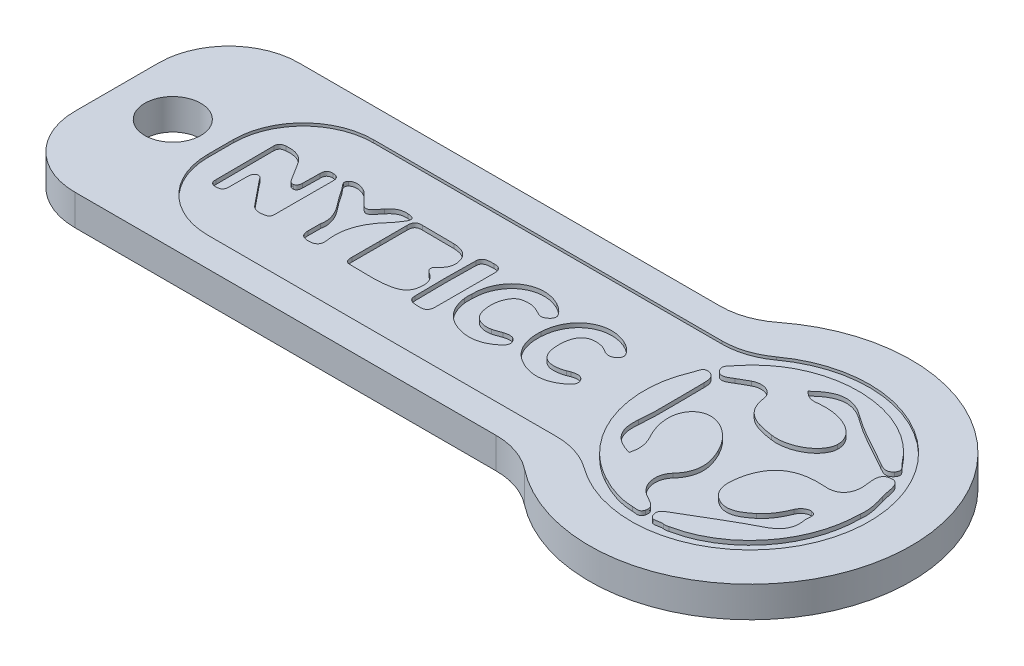
SolidWorks part; units mm, degrees
ref_plane "Plan de face" through (0, 0, 0) normal (0, 0, 1) x (1, 0, 0)
ref_plane "Plan de dessus" through (0, 0, 0) normal (0, 1, 0) x (1, 0, 0)
ref_plane "Plan de droite" through (0, 0, 0) normal (1, 0, 0) x (0, 0, -1)
sketch "Esquisse1" plane through (0, 0, 0) normal (0, 1, 0) x (1, 0, 0)
  line L0 (-14.5, 0) -> (0, 0) construction
  line L1 (-18.5, 8) -> (18.5, 8)
  line L2 (-18.5, 8) -> (-18.5, -8)
  line L3 (-18.5, -8) -> (18.5, -8)
  line L5 (-18.5, 8) -> (18.5, -8) construction
  line L6 (-18.5, -8) -> (18.5, 8) construction
  arc A0 (18.5, -8) -> (18.5, 8) centre (26.7614, 0) ccw
  circle A1 centre (-14.5, 0) radius 2
  point P0 (0, 0)
  dimension "D3" = 23
  dimension "D5" = 4
  dimension "D1" = 37
  dimension "D2" = 16
  dimension "D4" = 4
extrude "Boss.-Extru.1" add sketch "Esquisse1" along normal blind 2
sketch "Esquisse2" plane through (0, 2, 0) normal (0, 1, 0) x (1, 0, 0)
  line L0 (20.6551, -5.913) -> (-11.0872, -5.913)
  line L1 (-11.0872, -5.913) -> (-11.0872, 5.913)
  line L2 (-11.0872, 5.913) -> (20.6551, 5.913)
  line L3 (20.6551, 5.913) -> (20.5787, 5.7726)
  line L7 (18.5, 8) -> (-18.5, 8)
  line L8 (-18.5, 8) -> (-18.5, -8)
  line L9 (-18.5, -8) -> (18.5, -8)
  line L10 (18.5, 8) -> (-18.5, 8)
  line L11 (-18.5, 8) -> (-18.5, -8)
  line L12 (-18.5, -8) -> (18.5, -8)
  arc A2 (20.6551, -5.913) -> (20.6551, 5.913) centre (26.7614, 0) ccw
  arc A3 (20.6551, -5.913) -> (20.6551, 5.913) centre (26.7614, 0) ccw
  arc A4 (18.5, -8) -> (18.5, 8) centre (26.7614, 0) ccw
  arc A5 (18.5, -8) -> (18.5, 8) centre (26.7614, 0) ccw
  spline S0 degree 3 poles (0.225, -1.9246) (0.2286, -1.2609) (0.2275, -0.5975) (0.2283, 0.0661) knots 10 10 10 10 11 11 11 11
  spline S1 degree 3 poles (0.6284, -2.4527) (0.2813, -2.4644) (0.2234, -2.2089) (0.225, -1.9246) knots 9 9 9 9 10 10 10 10
  spline S2 degree 3 poles (3.5067, -2.3468) (2.5542, -2.5708) (1.5879, -2.4206) (0.6284, -2.4527) knots 8 8 8 8 9 9 9 9
  spline S3 degree 3 poles (4.4683, -1.5249) (4.3523, -2.028) (3.9703, -2.238) (3.5067, -2.3468) knots 7 7 7 7 8 8 8 8
  spline S4 degree 3 poles (4.0132, -0.175) (4.5319, -0.4973) (4.5922, -0.9877) (4.4683, -1.5249) knots 6 6 6 6 7 7 7 7
  spline S5 degree 3 poles (3.9341, 0.5259) (3.6149, 0.2483) (3.6818, 0.0309) (4.0132, -0.175) knots 5 5 5 5 6 6 6 6
  spline S6 degree 3 poles (4.2394, 1.8576) (4.4545, 1.3474) (4.3569, 0.8935) (3.9341, 0.5259) knots 4 4 4 4 5 5 5 5
  spline S7 degree 3 poles (3.0323, 2.5476) (3.5345, 2.5261) (4.0161, 2.3873) (4.2394, 1.8576) knots 3 3 3 3 4 4 4 4
  spline S8 degree 3 poles (0.7853, 2.5646) (1.5338, 2.5425) (2.2844, 2.5795) (3.0323, 2.5476) knots 2 2 2 2 3 3 3 3
  spline S9 degree 3 poles (0.2259, 1.9923) (0.215, 2.3984) (0.3606, 2.5772) (0.7853, 2.5646) knots 1 1 1 1 2 2 2 2
  spline S10 degree 3 poles (0.2283, 0.0661) (0.2291, 0.7082) (0.243, 1.3507) (0.2259, 1.9923) knots 0 0 0 0 1 1 1 1
  spline S11 degree 3 poles (-5.1722, 2.1197) (-5.1775, 1.4133) (-5.1754, 0.7068) (-5.176, 0.0003) knots 18 18 18 18 19 19 19 19
  spline S12 degree 3 poles (-5.6399, 2.5867) (-5.3196, 2.5835) (-5.1698, 2.4412) (-5.1722, 2.1197) knots 17 17 17 17 18 18 18 18
  spline S13 degree 3 poles (-6.0939, 2.115) (-6.0989, 2.4345) (-5.9709, 2.5902) (-5.6399, 2.5867) knots 16 16 16 16 17 17 17 17
  spline S14 degree 3 poles (-6.114, 0.896) (-6.0883, 1.3013) (-6.0877, 1.7087) (-6.0939, 2.115) knots 15 15 15 15 16 16 16 16
  spline S15 degree 3 poles (-6.3567, 0.4874) (-6.1454, 0.5282) (-6.1242, 0.7367) (-6.114, 0.896) knots 14 14 14 14 15 15 15 15
  spline S16 degree 3 poles (-6.7563, 0.7516) (-6.663, 0.6061) (-6.5561, 0.4488) (-6.3567, 0.4874) knots 13 13 13 13 14 14 14 14
  spline S17 degree 3 poles (-7.4724, 1.8877) (-7.2442, 1.5028) (-6.998, 1.1285) (-6.7563, 0.7516) knots 12 12 12 12 13 13 13 13
  spline S18 degree 3 poles (-8.9993, 2.5914) (-8.3468, 2.6534) (-7.8223, 2.4779) (-7.4724, 1.8877) knots 11 11 11 11 12 12 12 12
  spline S19 degree 3 poles (-9.4508, 2.1725) (-9.4369, 2.4583) (-9.2899, 2.5782) (-8.9993, 2.5914) knots 10 10 10 10 11 11 11 11
  spline S20 degree 3 poles (-9.4291, -2.0014) (-9.4372, -0.6101) (-9.4441, 0.7812) (-9.4508, 2.1725) knots 9 9 9 9 10 10 10 10
  spline S21 degree 3 poles (-9.0021, -2.437) (-9.2963, -2.4301) (-9.4357, -2.2901) (-9.4291, -2.0014) knots 8 8 8 8 9 9 9 9
  spline S22 degree 3 poles (-8.5069, -2.0014) (-8.512, -2.3343) (-8.6938, -2.4441) (-9.0021, -2.437) knots 7 7 7 7 8 8 8 8
  spline S23 degree 3 poles (-8.5036, -0.717) (-8.5043, -1.1452) (-8.5101, -1.5733) (-8.5069, -2.0014) knots 6 6 6 6 7 7 7 7
  spline S24 degree 3 poles (-8.2858, -0.219) (-8.4821, -0.3042) (-8.5032, -0.5178) (-8.5036, -0.717) knots 5 5 5 5 6 6 6 6
  spline S25 degree 3 poles (-7.8369, -0.4857) (-7.953, -0.3438) (-8.0529, -0.1181) (-8.2858, -0.219) knots 4 4 4 4 5 5 5 5
  spline S26 degree 3 poles (-6.4635, -2.1807) (-6.9172, -1.6123) (-7.376, -1.0481) (-7.8369, -0.4857) knots 3 3 3 3 4 4 4 4
  spline S27 degree 3 poles (-5.4688, -2.4272) (-5.8242, -2.5108) (-6.1923, -2.5206) (-6.4635, -2.1807) knots 2 2 2 2 3 3 3 3
  spline S28 degree 3 poles (-5.1794, -1.7337) (-5.182, -2.003) (-5.1008, -2.3406) (-5.4688, -2.4272) knots 1 1 1 1 2 2 2 2
  spline S29 degree 3 poles (-5.176, 0.0003) (-5.1766, -0.5777) (-5.174, -1.1557) (-5.1794, -1.7337) knots 0 0 0 0 1 1 1 1
  spline S30 degree 3 poles (14.6022, 1.5071) (13.5928, 1.7408) (13.0414, 1.2329) (13.0294, 0.0773) knots 11 11 11 11 12 12 12 12
  spline S31 degree 3 poles (15.1149, 1.2613) (14.9529, 1.3592) (14.7827, 1.4653) (14.6022, 1.5071) knots 10 10 10 10 11 11 11 11
  spline S32 degree 3 poles (15.9779, 1.4079) (15.76, 1.1539) (15.4505, 1.0583) (15.1149, 1.2613) knots 9 9 9 9 10 10 10 10
  spline S33 degree 3 poles (15.7902, 2.127) (15.9828, 1.9215) (16.214, 1.683) (15.9779, 1.4079) knots 8 8 8 8 9 9 9 9
  spline S34 degree 3 poles (15.1624, 2.5592) (15.3993, 2.452) (15.6134, 2.3158) (15.7902, 2.127) knots 7 7 7 7 8 8 8 8
  spline S35 degree 3 poles (11.588, 0.203) (11.6856, 2.2051) (13.4456, 3.3361) (15.1624, 2.5592) knots 6 6 6 6 7 7 7 7
  spline S36 degree 3 poles (12.9311, -2.3704) (11.8989, -1.8387) (11.5353, -0.8789) (11.588, 0.203) knots 5 5 5 5 6 6 6 6
  spline S37 degree 3 poles (15.6465, -2.1778) (14.7863, -2.8026) (13.8563, -2.8469) (12.9311, -2.3704) knots 4 4 4 4 5 5 5 5
  spline S38 degree 3 poles (16.0103, -1.3913) (16.2116, -1.7555) (15.9033, -1.9912) (15.6465, -2.1778) knots 3 3 3 3 4 4 4 4
  spline S39 degree 3 poles (15.1543, -1.1929) (15.4802, -1.0869) (15.8296, -1.0644) (16.0103, -1.3913) knots 2 2 2 2 3 3 3 3
  spline S40 degree 3 poles (14.9188, -1.2919) (14.9993, -1.2645) (15.0736, -1.2191) (15.1543, -1.1929) knots 1 1 1 1 2 2 2 2
  spline S41 degree 3 poles (13.0294, 0.0773) (13.0157, -1.2291) (13.6832, -1.7132) (14.9188, -1.2919) knots 0 0 0 0 1 1 1 1
  spline S42 degree 3 poles (6.7883, -0.4372) (6.7642, -0.2695) (6.7853, -0.0953) (6.7855, 0.0759) knots 13 13 13 13 14 14 14 14
  spline S43 degree 3 poles (8.2655, -2.4564) (7.3765, -2.0939) (6.9224, -1.3698) (6.7883, -0.4372) knots 12 12 12 12 13 13 13 13
  spline S44 degree 3 poles (10.8143, -2.1643) (10.0263, -2.763) (9.1527, -2.8182) (8.2655, -2.4564) knots 11 11 11 11 12 12 12 12
  spline S45 degree 3 poles (11.1531, -1.3675) (11.3657, -1.7257) (11.0713, -1.969) (10.8143, -2.1643) knots 10 10 10 10 11 11 11 11
  spline S46 degree 3 poles (10.2831, -1.1939) (10.6037, -1.0968) (10.9594, -1.0413) (11.1531, -1.3675) knots 9 9 9 9 10 10 10 10
  spline S47 degree 3 poles (9.6778, -1.3958) (9.8846, -1.3539) (10.0795, -1.2556) (10.2831, -1.1939) knots 8 8 8 8 9 9 9 9
  spline S48 degree 3 poles (8.2731, -0.709) (8.4644, -1.2666) (8.9952, -1.5338) (9.6778, -1.3958) knots 7 7 7 7 8 8 8 8
  spline S49 degree 3 poles (8.7857, 1.4455) (8.2295, 1.1729) (7.9857, 0.1288) (8.2731, -0.709) knots 6 6 6 6 7 7 7 7
  spline S50 degree 3 poles (9.155, 1.5328) (9.0302, 1.5112) (8.8966, 1.4998) (8.7857, 1.4455) knots 5 5 5 5 6 6 6 6
  spline S51 degree 3 poles (10.3714, 1.2365) (9.9944, 1.4594) (9.6027, 1.6104) (9.155, 1.5328) knots 4 4 4 4 5 5 5 5
  spline S52 degree 3 poles (11.1159, 1.4051) (10.9208, 1.1953) (10.6661, 1.0622) (10.3714, 1.2365) knots 3 3 3 3 4 4 4 4
  spline S53 degree 3 poles (10.9947, 2.0797) (11.1716, 1.8988) (11.3491, 1.6561) (11.1159, 1.4051) knots 2 2 2 2 3 3 3 3
  spline S54 degree 3 poles (10.3813, 2.5334) (10.6062, 2.4205) (10.8187, 2.2596) (10.9947, 2.0797) knots 1 1 1 1 2 2 2 2
  spline S55 degree 3 poles (6.7855, 0.0759) (6.7712, 2.1623) (8.6141, 3.4209) (10.3813, 2.5334) knots 0 0 0 0 1 1 1 1
  spline S56 degree 3 poles (20.8247, -2.0529) (20.69, -3.4272) (21.2917, -4.0532) (22.4958, -4.411) knots 13 13 13 13 14 14 14 14
  spline S57 degree 3 poles (20.8707, 2.5877) (20.8518, 1.04) (20.975, -0.5195) (20.8247, -2.0529) knots 12 12 12 12 13 13 13 13
  spline S58 degree 3 poles (20.3589, 3.4373) (20.7757, 3.356) (20.8759, 3.0031) (20.8707, 2.5877) knots 11 11 11 11 12 12 12 12
  spline S59 degree 3 poles (19.7877, 2.7925) (19.904, 3.0638) (19.9018, 3.5264) (20.3589, 3.4373) knots 10 10 10 10 11 11 11 11
  spline S60 degree 3 poles (23.1867, -6.7698) (19.8096, -4.9332) (18.3001, -0.6793) (19.7877, 2.7925) knots 9 9 9 9 10 10 10 10
  spline S61 degree 3 poles (25.9567, -7.6289) (24.9549, -7.6033) (24.0484, -7.2383) (23.1867, -6.7698) knots 8 8 8 8 9 9 9 9
  spline S62 degree 3 poles (26.6612, -7.3752) (26.5599, -7.7864) (26.214, -7.6353) (25.9567, -7.6289) knots 7 7 7 7 8 8 8 8
  spline S63 degree 3 poles (26.268, -6.6952) (26.5299, -6.8467) (26.7435, -7.0408) (26.6612, -7.3752) knots 6 6 6 6 7 7 7 7
  spline S64 degree 3 poles (25.7401, -6.3888) (25.9117, -6.4978) (26.0918, -6.5935) (26.268, -6.6952) knots 5 5 5 5 6 6 6 6
  spline S65 degree 3 poles (25.3508, -4.1307) (24.7364, -4.8112) (24.986, -5.9092) (25.7401, -6.3888) knots 4 4 4 4 5 5 5 5
  spline S66 degree 3 poles (25.5618, -1.0872) (26.0741, -2.135) (26.252, -3.1326) (25.3508, -4.1307) knots 3 3 3 3 4 4 4 4
  spline S67 degree 3 poles (22.5765, 0.6204) (23.5077, 1.0885) (24.8768, 0.3142) (25.5618, -1.0872) knots 2 2 2 2 3 3 3 3
  spline S68 degree 3 poles (22.2705, -2.6617) (21.4852, -1.2334) (21.6533, 0.1562) (22.5765, 0.6204) knots 1 1 1 1 2 2 2 2
  spline S69 degree 3 poles (22.4958, -4.411) (22.6895, -3.7654) (22.5874, -3.2375) (22.2705, -2.6617) knots 0 0 0 0 1 1 1 1
  spline S70 degree 3 poles (34.2908, 1.9196) (34.5116, 1.2692) (34.6572, 0.5833) (34.5723, 0.043) knots 15 15 15 15 16 16 16 16
  spline S71 degree 3 poles (33.4768, 3.345) (34.1825, 3.4033) (34.1107, 2.4507) (34.2908, 1.9196) knots 14 14 14 14 15 15 15 15
  spline S72 degree 3 poles (32.9899, 1.8117) (32.9782, 2.3605) (32.6504, 3.2769) (33.4768, 3.345) knots 13 13 13 13 14 14 14 14
  spline S73 degree 3 poles (31.6503, 0.4778) (32.418, 0.4191) (33.0107, 0.8361) (32.9899, 1.8117) knots 12 12 12 12 13 13 13 13
  spline S74 degree 3 poles (28.0087, -2.0014) (28.3864, -0.1074) (29.5871, 0.6354) (31.6503, 0.4778) knots 11 11 11 11 12 12 12 12
  spline S75 degree 3 poles (28.7232, -4.1459) (27.8705, -3.6814) (27.8418, -2.8385) (28.0087, -2.0014) knots 10 10 10 10 11 11 11 11
  spline S76 degree 3 poles (30.8285, -3.6402) (30.2151, -4.1482) (29.5238, -4.582) (28.7232, -4.1459) knots 9 9 9 9 10 10 10 10
  spline S77 degree 3 poles (31.9149, -2.0477) (31.6643, -2.6604) (31.3386, -3.2179) (30.8285, -3.6402) knots 8 8 8 8 9 9 9 9
  spline S78 degree 3 poles (32.6672, -1.5283) (32.3502, -1.494) (32.0434, -1.7332) (31.9149, -2.0477) knots 7 7 7 7 8 8 8 8
  spline S79 degree 3 poles (32.9603, -2.3153) (32.9084, -2.0339) (33.1548, -1.5813) (32.6672, -1.5283) knots 6 6 6 6 7 7 7 7
  spline S80 degree 3 poles (31.9014, -4.2266) (32.7588, -3.7947) (33.1312, -3.2385) (32.9603, -2.3153) knots 5 5 5 5 6 6 6 6
  spline S81 degree 3 poles (27.7784, -6.5813) (29.1518, -5.7938) (30.49, -4.9378) (31.9014, -4.2266) knots 4 4 4 4 5 5 5 5
  spline S82 degree 3 poles (27.221, -7.3854) (27.066, -6.9234) (27.4568, -6.7657) (27.7784, -6.5813) knots 3 3 3 3 4 4 4 4
  spline S83 degree 3 poles (28.1667, -7.6063) (27.8477, -7.5375) (27.3951, -7.903) (27.221, -7.3854) knots 2 2 2 2 3 3 3 3
  spline S84 degree 3 poles (28.5281, -7.569) (28.4093, -7.5932) (28.2794, -7.6307) (28.1667, -7.6063) knots 1 1 1 1 2 2 2 2
  spline S85 degree 3 poles (34.5723, 0.043) (34.5572, -3.6847) (31.9805, -6.8615) (28.5281, -7.569) knots 0 0 0 0 1 1 1 1
  spline S86 degree 3 poles (-2.9715, -1.8867) (-2.973, -1.6296) (-2.9712, -1.3724) (-2.9707, -0.9865) knots 12 12 12 12 13 13 13 13
  spline S87 degree 3 poles (-2.3827, -2.4792) (-2.7888, -2.4647) (-2.9692, -2.2761) (-2.9715, -1.8867) knots 11 11 11 11 12 12 12 12
  spline S88 degree 3 poles (-1.7083, -1.7964) (-1.6343, -2.2893) (-1.886, -2.4971) (-2.3827, -2.4792) knots 10 10 10 10 11 11 11 11
  spline S89 degree 3 poles (-0.5499, 1.5886) (-1.4324, 0.6279) (-1.9089, -0.4619) (-1.7083, -1.7964) knots 9 9 9 9 10 10 10 10
  spline S90 degree 3 poles (-0.1364, 2.159) (-0.265, 1.9625) (-0.392, 1.7605) (-0.5499, 1.5886) knots 8 8 8 8 9 9 9 9
  spline S91 degree 3 poles (-0.4448, 2.7623) (0.0585, 2.7305) (0.1083, 2.5327) (-0.1364, 2.159) knots 7 7 7 7 8 8 8 8
  spline S92 degree 3 poles (-1.5894, 2.2197) (-1.281, 2.6095) (-0.9475, 2.7942) (-0.4448, 2.7623) knots 6 6 6 6 7 7 7 7
  spline S93 degree 3 poles (-2.9946, 2.1544) (-2.2746, 1.3894) (-2.2599, 1.3721) (-1.5894, 2.2197) knots 5 5 5 5 6 6 6 6
  spline S94 degree 3 poles (-3.569, 2.6592) (-3.3482, 2.549) (-3.1695, 2.3403) (-2.9946, 2.1544) knots 4 4 4 4 5 5 5 5
  spline S95 degree 3 poles (-4.5969, 2.6437) (-4.3452, 2.899) (-3.899, 2.8238) (-3.569, 2.6592) knots 3 3 3 3 4 4 4 4
  spline S96 degree 3 poles (-4.318, 1.8864) (-4.4694, 2.1215) (-4.86, 2.3768) (-4.5969, 2.6437) knots 2 2 2 2 3 3 3 3
  spline S97 degree 3 poles (-3.6134, 0.892) (-3.8691, 1.2068) (-4.0981, 1.5451) (-4.318, 1.8864) knots 1 1 1 1 2 2 2 2
  spline S98 degree 3 poles (-2.9707, -0.9865) (-2.8232, -0.3301) (-3.1349, 0.3025) (-3.6134, 0.892) knots 0 0 0 0 1 1 1 1
  spline S99 degree 3 poles (28.4489, 6.1036) (27.188, 7.04) (26.1934, 6.8331) (25.1006, 5.7726) knots 13 13 13 13 14 14 14 14
  spline S100 degree 3 poles (32.2257, 3.8741) (30.9697, 4.6247) (29.6158, 5.2371) (28.4489, 6.1036) knots 12 12 12 12 13 13 13 13
  spline S101 degree 3 poles (33.1947, 3.8749) (32.8996, 3.5244) (32.5762, 3.6646) (32.2257, 3.8741) knots 11 11 11 11 12 12 12 12
  spline S102 degree 3 poles (32.9181, 4.6879) (33.0852, 4.4632) (33.51, 4.2491) (33.1947, 3.8749) knots 10 10 10 10 11 11 11 11
  spline S103 degree 3 poles (21.0052, 4.8289) (23.9283, 8.5635) (30.0923, 8.4884) (32.9181, 4.6879) knots 9 9 9 9 10 10 10 10
  spline S104 degree 3 poles (20.6512, 3.9116) (20.3706, 4.3111) (20.8091, 4.5784) (21.0052, 4.8289) knots 8 8 8 8 9 9 9 9
  spline S105 degree 3 poles (21.7112, 3.951) (21.3602, 3.7373) (20.9758, 3.4496) (20.6512, 3.9116) knots 7 7 7 7 8 8 8 8
  spline S106 degree 3 poles (22.4531, 4.3729) (22.1989, 4.2458) (21.9541, 4.099) (21.7112, 3.951) knots 6 6 6 6 7 7 7 7
  spline S107 degree 3 poles (23.9755, 3.7431) (23.8907, 4.348) (23.204, 4.7486) (22.4531, 4.3729) knots 5 5 5 5 6 6 6 6
  spline S108 degree 3 poles (26.5035, 1.7576) (25.3358, 1.9291) (24.1957, 2.1695) (23.9755, 3.7431) knots 4 4 4 4 5 5 5 5
  spline S109 degree 3 poles (29.457, 3.5205) (29.4094, 2.5046) (27.9199, 1.5498) (26.5035, 1.7576) knots 3 3 3 3 4 4 4 4
  spline S110 degree 3 poles (26.7445, 5.4024) (28.3033, 5.391) (29.5054, 4.5538) (29.457, 3.5205) knots 2 2 2 2 3 3 3 3
  spline S111 degree 3 poles (26.0136, 5.3603) (26.2569, 5.3802) (26.5009, 5.4042) (26.7445, 5.4024) knots 1 1 1 1 2 2 2 2
  spline S112 degree 3 poles (25.1006, 5.7726) (25.3972, 5.4799) (25.6664, 5.3319) (26.0136, 5.3603) knots 0 0 0 0 1 1 1 1
  spline S113 degree 3 poles (6.2957, 2.1656) (6.2889, 1.4614) (6.2923, 0.7571) (6.2917, 0.0529) knots 6 6 6 6 7 7 7 7
  spline S114 degree 3 poles (5.7113, 2.7436) (6.1126, 2.754) (6.2995, 2.5672) (6.2957, 2.1656) knots 5 5 5 5 6 6 6 6
  spline S115 degree 3 poles (4.8778, 2.2684) (4.8908, 2.7581) (5.3424, 2.734) (5.7113, 2.7436) knots 4 4 4 4 5 5 5 5
  spline S116 degree 3 poles (4.8746, -2.0826) (4.8408, -0.6328) (4.8396, 0.8188) (4.8778, 2.2684) knots 3 3 3 3 4 4 4 4
  spline S117 degree 3 poles (5.7365, -2.5991) (5.3325, -2.5938) (4.8868, -2.606) (4.8746, -2.0826) knots 2 2 2 2 3 3 3 3
  spline S118 degree 3 poles (6.2899, -1.9959) (6.2905, -2.369) (6.1719, -2.6048) (5.7365, -2.5991) knots 1 1 1 1 2 2 2 2
  spline S119 degree 3 poles (6.2917, 0.0529) (6.2911, -0.63) (6.2888, -1.313) (6.2899, -1.9959) knots 0 0 0 0 1 1 1 1
  dimension "D1" = 3
  dimension "D2" = 0
sketch "Esquisse3" plane through (0, 2, 0) normal (0, 1, 0) x (1, 0, 0)
  line L0 (-18.5, -8) -> (18.5, -8) construction
  line L1 (18.5, 8) -> (-18.5, 8) construction
  line L2 (-18.5, 8) -> (-18.5, -8) construction
  line L3 (-18.5, -8) -> (18.5, -8)
  line L4 (18.5, 8) -> (-18.5, 8)
  line L5 (-18.5, 8) -> (-18.5, -8)
  line L6 (20.6551, -5.913) -> (-11.0872, -5.913) construction
  line L7 (-11.0872, -5.913) -> (-11.0872, 5.913) construction
  line L8 (-11.0872, 5.913) -> (20.6551, 5.913) construction
  line L9 (20.6551, -5.913) -> (-11.0872, -5.913)
  line L10 (-11.0872, -5.913) -> (-11.0872, 5.913)
  line L11 (-11.0872, 5.913) -> (20.6551, 5.913)
  arc A0 (18.5, -8) -> (18.5, 8) centre (26.7614, 0) ccw construction
  arc A1 (18.5, -8) -> (18.5, 8) centre (26.7614, 0) ccw
  arc A2 (20.6551, -5.913) -> (20.6551, 5.913) centre (26.7614, 0) ccw construction
  arc A3 (20.6551, -5.913) -> (20.6551, 5.913) centre (26.7614, 0) ccw
  circle A4 centre (-14.5, 0) radius 2 construction
  circle A5 centre (-14.5, 0) radius 2
extrude "Boss.-Extru.2" add sketch "Esquisse3" along normal blind 0.2
sketch "Esquisse4" plane through (0, 2, 0) normal (0, 1, 0) x (1, 0, 0)
  line L0 (20.6551, 5.913) -> (20.5787, 5.7726) construction
  line L7 (20.6551, 5.913) -> (20.5787, 5.7726)
  spline S0 degree 3 poles (-2982.0321, -306.2248) (2982.2581, 103.2699) (-2981.6444, -105.1439) (2982.0145, 307.7935) knots -65.695393 -65.695393 -65.695393 -65.695393 87.11992 87.11992 87.11992 87.11992 only from (0.225, -1.9246) to (0.2283, 0.0661) construction
  spline S1 degree 3 poles (2999.5682, 0.4278) (-2999.8564, -103.9529) (3000.3037, 105.1379) (-2999.0596, 1.1227) knots -40.537107 -40.537107 -40.537107 -40.537107 41.130987 41.130987 41.130987 41.130987 only from (0.2283, 0.0661) to (0.2259, 1.9923) construction
  spline S2 degree 3 poles (-2594.1466, -1484.3682) (2742.4634, 1004.8177) (-2871.3247, -600.9655) (2983.9031, 280.5652) knots -27.989827 -27.989827 -27.989827 -27.989827 28.752727 28.752727 28.752727 28.752727 only from (0.2259, 1.9923) to (0.7853, 2.5646) construction
  spline S3 degree 3 poles (51.5824, 3001.694) (-133.9703, -2997.156) (137.8597, 3002.2619) (-48.6688, -2996.538) knots -26.157281 -26.157281 -26.157281 -26.157281 31.080499 31.080499 31.080499 31.080499 only from (0.7853, 2.5646) to (3.0323, 2.5476) construction
  spline S4 degree 3 poles (2009.6493, 2232.5005) (-2006.0549, -2261.7938) (1972.7573, 2299.3914) (-1888.9186, -2324.9431) knots -17.557346 -17.557346 -17.557346 -17.557346 22.989169 22.989169 22.989169 22.989169 only from (3.0323, 2.5476) to (4.2394, 1.8576) construction
  spline S5 degree 3 poles (-825.3245, -2787.801) (-643.4265, 2631.1826) (1608.761, -2358.0246) (-2178.4925, 2039.7568) knots -43.629744 -43.629744 -43.629744 -43.629744 43.39188 43.39188 43.39188 43.39188 only from (4.2394, 1.8576) to (3.9341, 0.5259) construction
  spline S6 degree 3 poles (2844.7759, 963.7921) (-2876.8731, -1060.506) (2838.2734, 1189.6036) (-2665.5674, -1363.5437) knots -20.650114 -20.650114 -20.650114 -20.650114 36.446421 36.446421 36.446421 36.446421 only from (3.9341, 0.5259) to (4.0132, -0.175) construction
  spline S7 degree 3 poles (-2766.0668, -1151.1511) (2784.3818, 1220.8463) (-2765.0092, -1253.3988) (2740.6322, 1228.3167) knots -13.985195 -13.985195 -13.985195 -13.985195 29.240127 29.240127 29.240127 29.240127 only from (4.0132, -0.175) to (4.4683, -1.5249) construction
  spline S8 degree 3 poles (-2041.5863, 2192.2627) (2100.3276, -2184.7351) (-2103.0074, 2172.4151) (2071.9559, -2174.9533) knots -13.982728 -13.982728 -13.982728 -13.982728 30.958336 30.958336 30.958336 30.958336 only from (4.4683, -1.5249) to (3.5067, -2.3468) construction
  spline S9 degree 3 poles (-59.3201, 2996.7539) (129.9649, -3003.5516) (-126.8548, 2998.569) (62.5749, -3001.4884) knots -8.86397 -8.86397 -8.86397 -8.86397 26.208592 26.208592 26.208592 26.208592 only from (3.5067, -2.3468) to (0.6284, -2.4527) construction
  spline S10 degree 3 poles (2111.4901, 2129.1121) (-2098.1565, -2170.5449) (2084.4213, 2180.9807) (-2068.4391, -2174.5205) knots -10.690662 -10.690662 -10.690662 -10.690662 31.066809 31.066809 31.066809 31.066809 only from (0.6284, -2.4527) to (0.225, -1.9246) construction
  spline S11 degree 3 poles (-348.132, -2949.361) (1153.6825, 2295.7904) (-1977.1505, -1448.0147) (2927.5221, 384.2302) knots -14.264316 -14.264316 -14.264316 -14.264316 39.479423 39.479423 39.479423 39.479423 only from (14.6022, 1.5071) to (13.0294, 0.0773) construction
  spline S12 degree 3 poles (2948.4033, 347.3048) (-2187.816, 787.9674) (1421.8733, -1874.4898) (-543.1272, 2902.7051) knots -24.639929 -24.639929 -24.639929 -24.639929 25.558939 25.558939 25.558939 25.558939 only from (13.0294, 0.0773) to (14.9188, -1.2919) construction
  spline S13 degree 3 poles (-958.1483, 2836.3928) (974.8222, -2845.1141) (-944.5177, 2842.7267) (987.4974, -2839.1796) knots -40.965757 -40.965757 -40.965757 -40.965757 43.934538 43.934538 43.934538 43.934538 only from (14.9188, -1.2919) to (15.1543, -1.1929) construction
  spline S14 degree 3 poles (1834.0952, 2384.2611) (-1781.7103, -2431.8551) (1763.0904, 2463.8486) (-1658.2791, -2490.2535) knots -19.116516 -19.116516 -19.116516 -19.116516 22.783936 22.783936 22.783936 22.783936 only from (15.1543, -1.1929) to (16.0103, -1.3913) construction
  spline S15 degree 3 poles (-2944.9557, 480.1005) (2999.5577, -437.1195) (-2973.0865, 399.1902) (2991.1962, -383.3809) knots -13.526295 -13.526295 -13.526295 -13.526295 21.371458 21.371458 21.371458 21.371458 only from (16.0103, -1.3913) to (15.6465, -2.1778) construction
  spline S16 degree 3 poles (-1566.3264, 2534.7247) (2051.528, -2222.9537) (-2481.2826, 1586.895) (2909.5968, -512.0463) knots -23.179984 -23.179984 -23.179984 -23.179984 39.168029 39.168029 39.168029 39.168029 only from (15.6465, -2.1778) to (12.9311, -2.3704) construction
  spline S17 degree 3 poles (2137.7771, 2113.1028) (-2015.8157, -2312.7506) (1896.5246, 2442.5114) (-1679.2144, -2476.4052) knots -12.834342 -12.834342 -12.834342 -12.834342 26.665789 26.665789 26.665789 26.665789 only from (12.9311, -2.3704) to (11.588, 0.203) construction
  spline S18 degree 3 poles (2839.5821, 979.7641) (-2656.3811, -1375.7454) (2464.1202, 1739.6498) (-2161.0995, -2052.3909) knots -4.94192 -4.94192 -4.94192 -4.94192 17.913939 17.913939 17.913939 17.913939 only from (11.588, 0.203) to (15.1624, 2.5592) construction
  spline S19 degree 3 poles (1510.985, 2602.6074) (-1552.1611, -2572.6268) (1598.0144, 2567.9488) (-1535.4163, -2565.4835) knots -41.995983 -41.995983 -41.995983 -41.995983 53.363625 53.363625 53.363625 53.363625 only from (15.1624, 2.5592) to (15.7902, 2.127) construction
  spline S20 degree 3 poles (3015.6348, 2.4047) (-2997.8609, -4.8648) (3029.2533, 30.8991) (-2983.1374, -63.8689) knots -10.045119 -10.045119 -10.045119 -10.045119 26.196193 26.196193 26.196193 26.196193 only from (15.7902, 2.127) to (15.9779, 1.4079) construction
  spline S21 degree 3 poles (-1549.1347, -2555.3428) (1391.783, 2695.2672) (-1162.449, -2783.2851) (991.3263, 2836.1786) knots -18.58527 -18.58527 -18.58527 -18.58527 35.231852 35.231852 35.231852 35.231852 only from (15.9779, 1.4079) to (15.1149, 1.2613) construction
  spline S22 degree 3 poles (95.5079, 3000.0856) (-62.8496, -3010.3393) (113.121, 3012.0828) (-125.8263, -2994.9698) knots -24.511096 -24.511096 -24.511096 -24.511096 44.727739 44.727739 44.727739 44.727739 only from (15.1149, 1.2613) to (14.6022, 1.5071) construction
  spline S23 degree 3 poles (2991.3697, 111.9861) (-3001.8516, 37.0039) (2991.5458, -37.9783) (-3001.8604, -112.9605) knots -64.579708 -64.579708 -64.579708 -64.579708 65.141973 65.141973 65.141973 65.141973 only from (-5.176, 0.0003) to (-5.1794, -1.7337) construction
  spline S24 degree 3 poles (2989.89, 135.626) (-3000.2375, 54.0237) (2989.8547, -53.0066) (-3000.1489, -134.048) knots -47.926681 -47.926681 -47.926681 -47.926681 85.380927 85.380927 85.380927 85.380927 only from (-5.1722, 2.1197) to (-5.176, 0.0003) construction
  spline S25 degree 3 poles (-2153.2815, 2064.2448) (1424.0711, -2402.4044) (-836.3022, 2709.862) (331.7858, -2969.2518) knots -23.860655 -23.860655 -23.860655 -23.860655 55.723257 55.723257 55.723257 55.723257 only from (-5.6399, 2.5867) to (-5.1722, 2.1197) construction
  spline S26 degree 3 poles (-2850.7548, -910.9558) (2919.3178, 374.5288) (-2974.0352, 38.0522) (2972.4393, -333.115) knots -20.378659 -20.378659 -20.378659 -20.378659 49.105246 49.105246 49.105246 49.105246 only from (-6.0939, 2.115) to (-5.6399, 2.5867) construction
  spline S27 degree 3 poles (-2970.5078, 457.8634) (2958.2056, -555.3162) (-2968.3508, 574.2394) (2952.1212, -494.1318) knots -38.421322 -38.421322 -38.421322 -38.421322 71.156716 71.156716 71.156716 71.156716 only from (-6.114, 0.896) to (-6.0939, 2.115) construction
  spline S28 degree 3 poles (-1965.1544, 2272.4229) (1921.8618, -2310.2499) (-1904.3367, 2336.6874) (1863.6352, -2344.9971) knots -7.139946 -7.139946 -7.139946 -7.139946 36.92124 36.92124 36.92124 36.92124 only from (-6.3567, 0.4874) to (-6.114, 0.896) construction
  spline S29 degree 3 poles (-1054.9441, -2810.0063) (1050.367, 2818.4842) (-1081.7562, -2810.0805) (1095.1224, 2790.7133) knots -10.807958 -10.807958 -10.807958 -10.807958 36.862166 36.862166 36.862166 36.862166 only from (-6.7563, 0.7516) to (-6.3567, 0.4874) construction
  spline S30 degree 3 poles (2543.5555, 1579.5535) (-2604.8686, -1503.9322) (2591.2874, 1505.5793) (-2558.0032, -1576.7089) knots -35.938353 -35.938353 -35.938353 -35.938353 61.545934 61.545934 61.545934 61.545934 only from (-7.4724, 1.8877) to (-6.7563, 0.7516) construction
  spline S31 degree 3 poles (567.7958, 2945.1059) (-767.2962, -2960.8783) (822.8027, 2943.5513) (-833.8392, -2882.0037) knots -15.937915 -15.937915 -15.937915 -15.937915 35.0837 35.0837 35.0837 35.0837 only from (-8.9993, 2.5914) to (-7.4724, 1.8877) construction
  spline S32 degree 3 poles (28.4644, -2993.879) (277.6471, 2932.9339) (-709.155, -2839.7103) (1208.0554, 2732.3375) knots -24.232003 -24.232003 -24.232003 -24.232003 48.696631 48.696631 48.696631 48.696631 only from (-9.4508, 2.1725) to (-8.9993, 2.5914) construction
  spline S33 degree 3 poles (2857.7069, -776.2907) (-2871.2407, 20.2347) (2850.6659, -17.9582) (-2871.6017, 789.4215) knots -127.155557 -127.155557 -127.155557 -127.155557 147.31009 147.31009 147.31009 147.31009 only from (-9.4291, -2.0014) to (-9.4508, 2.1725) construction
  spline S34 degree 3 poles (2693.2721, -1196.6217) (-1648.8695, 1860.0323) (735.4754, -2458.2345) (-6.8346, 2977.8397) knots -45.248039 -45.248039 -45.248039 -45.248039 58.347774 58.347774 58.347774 58.347774 only from (-9.0021, -2.437) to (-9.4291, -2.0014) construction
  spline S35 degree 3 poles (-1406.3726, 2652.1823) (1348.518, -2718.4862) (-1267.9012, 2761.4218) (1077.8974, -2797.2123) knots -20.18475 -20.18475 -20.18475 -20.18475 38.895479 38.895479 38.895479 38.895479 only from (-8.5069, -2.0014) to (-9.0021, -2.437) construction
  spline S36 degree 3 poles (-3006.376, 94.5843) (2989.9983, 5.7059) (-3007.0337, -8.4595) (2989.4363, -95.7513) knots -53.348757 -53.348757 -53.348757 -53.348757 66.067261 66.067261 66.067261 66.067261 only from (-8.5036, -0.717) to (-8.5069, -2.0014) construction
  spline S37 degree 3 poles (2229.893, -1997.5388) (-2227.3921, 2036.8085) (2190.8139, -2059.7449) (-2188.1871, 2060.4819) knots -18.254974 -18.254974 -18.254974 -18.254974 30.309368 30.309368 30.309368 30.309368 only from (-8.2858, -0.219) to (-8.5036, -0.717) construction
  spline S38 degree 3 poles (1012.8533, 2820.4962) (-1028.9415, -2830.0317) (1022.1983, 2825.8867) (-1055.8507, -2811.2383) knots -14.827096 -14.827096 -14.827096 -14.827096 23.213079 23.213079 23.213079 23.213079 only from (-7.8369, -0.4857) to (-8.2858, -0.219) construction
  spline S39 degree 3 poles (-2264.28, -1971.6814) (2418.2632, 1764.7617) (-2437.7743, -1760.9741) (2252.1522, 1966.117) knots -87.097842 -87.097842 -87.097842 -87.097842 96.535082 96.535082 96.535082 96.535082 only from (-6.4635, -2.1807) to (-7.8369, -0.4857) construction
  spline S40 degree 3 poles (-1146.2684, -2776.9723) (1131.44, 2794.2873) (-1107.7125, -2812.167) (1033.1633, 2811.6903) knots -19.874716 -19.874716 -19.874716 -19.874716 23.440495 23.440495 23.440495 23.440495 only from (-5.4688, -2.4272) to (-6.4635, -2.1807) construction
  spline S41 degree 3 poles (2568.0048, -1543.9665) (-2583.5789, 1551.7322) (2577.7396, -1547.8337) (-2591.8951, 1517.2547) knots -15.744794 -15.744794 -15.744794 -15.744794 18.088642 18.088642 18.088642 18.088642 only from (-5.1794, -1.7337) to (-5.4688, -2.4272) construction
  spline S42 degree 3 poles (-2958.381, 423.5428) (3002.5799, -381.3482) (-2985.0311, 344.8063) (2992.5981, -330.9635) knots -6.698907 -6.698907 -6.698907 -6.698907 28.58634 28.58634 28.58634 28.58634 only from (11.1531, -1.3675) to (10.8143, -2.1643) construction
  spline S43 degree 3 poles (1554.7818, 2570.4885) (-1524.6632, -2600.5468) (1510.5046, 2617.8559) (-1430.408, -2632.0808) knots -10.76817 -10.76817 -10.76817 -10.76817 28.672218 28.672218 28.672218 28.672218 only from (10.2831, -1.1939) to (11.1531, -1.3675) construction
  spline S44 degree 3 poles (-655.9986, 2923.7516) (651.9477, -2935.6544) (-632.9831, 2932.8279) (679.4642, -2925.4989) knots -22.986962 -22.986962 -22.986962 -22.986962 40.197873 40.197873 40.197873 40.197873 only from (9.6778, -1.3958) to (10.2831, -1.1939) construction
  spline S45 degree 3 poles (2856.4587, -916.4314) (-2637.9023, 1335.4528) (2404.0422, -1745.3084) (-2083.0988, 2134.9347) knots -16.1158 -16.1158 -16.1158 -16.1158 31.351771 31.351771 31.351771 31.351771 only from (8.2731, -0.709) to (9.6778, -1.3958) construction
  spline S46 degree 3 poles (-360.8692, -2974.2022) (571.4544, 2981.2626) (-747.8209, -2937.5614) (955.1924, 2844.0583) knots -7.761652 -7.761652 -7.761652 -7.761652 21.126773 21.126773 21.126773 21.126773 only from (8.7857, 1.4455) to (8.2731, -0.709) construction
  spline S47 degree 3 poles (-1516.2115, 2584.7093) (1547.558, -2581.8978) (-1524.05, 2588.0367) (1518.2782, -2590.9675) knots -31.275404 -31.275404 -31.275404 -31.275404 41.704134 41.704134 41.704134 41.704134 only from (9.155, 1.5328) to (8.7857, 1.4455) construction
  spline S48 degree 3 poles (820.6755, 2889.4774) (-753.5804, -2916.3367) (769.4511, 2919.6859) (-781.2622, -2892.292) knots -22.942366 -22.942366 -22.942366 -22.942366 30.037319 30.037319 30.037319 30.037319 only from (10.3714, 1.2365) to (9.155, 1.5328) construction
  spline S49 degree 3 poles (-343.7483, -2977.2703) (308.1702, 3008.3894) (-212.7774, -3010.8971) (147.8081, 2997.7206) knots -20.842434 -20.842434 -20.842434 -20.842434 26.221229 26.221229 26.221229 26.221229 only from (11.1159, 1.4051) to (10.3714, 1.2365) construction
  spline S50 degree 3 poles (2977.588, -443.9598) (-2974.9457, 416.7555) (3002.6336, -367.0798) (-2972.6097, 311.4831) knots -17.340012 -17.340012 -17.340012 -17.340012 21.379784 21.379784 21.379784 21.379784 only from (10.9947, 2.0797) to (11.1159, 1.4051) construction
  spline S51 degree 3 poles (1746.6078, -2442.7306) (-1872.7626, 2381.3018) (2009.4208, -2281.8479) (-2069.6362, 2161.9686) knots -41.281471 -41.281471 -41.281471 -41.281471 44.823321 44.823321 44.823321 44.823321 only from (10.3813, 2.5334) to (10.9947, 2.0797) construction
  spline S52 degree 3 poles (2773.0057, 1143.5896) (-2584.4348, -1521.2222) (2371.2938, 1862.3972) (-2071.5977, -2148.7592) knots -10.385418 -10.385418 -10.385418 -10.385418 11.301025 11.301025 11.301025 11.301025 only from (6.7855, 0.0759) to (10.3813, 2.5334) construction
  spline S53 degree 3 poles (2979.5687, 402.4884) (-2966.9556, -427.1046) (2980.4966, 426.9029) (-2965.9429, -402.5793) knots -21.855628 -21.855628 -21.855628 -21.855628 49.223658 49.223658 49.223658 49.223658 only from (6.7883, -0.4372) to (6.7855, 0.0759) construction
  spline S54 degree 3 poles (2007.7271, 2232.2382) (-1927.0081, -2443.1365) (1813.7271, 2559.8061) (-1598.3545, -2533.7182) knots -10.372644 -10.372644 -10.372644 -10.372644 40.161907 40.161907 40.161907 40.161907 only from (8.2655, -2.4564) to (6.7883, -0.4372) construction
  spline S55 degree 3 poles (-1101.4373, 2781.1181) (1421.9667, -2807.2673) (-1678.6973, 2674.0482) (1890.9524, -2330.7888) knots -13.173982 -13.173982 -13.173982 -13.173982 42.267473 42.267473 42.267473 42.267473 only from (10.8143, -2.1643) to (8.2655, -2.4564) construction
  spline S86 degree 3 poles (-2996.4431, 152.39) (2950.5158, 121.4106) (-2932.3411, -386.8471) (2923.4592, 656.5887) knots -7.467958 -7.467958 -7.467958 -7.467958 18.404267 18.404267 18.404267 18.404267 only from (-2.9946, 2.1544) to (-1.5894, 2.2197) construction
  spline S87 degree 3 poles (-952.1225, -2843.2164) (909.3004, 2874.942) (-899.1265, -2875.8655) (896.9632, 2863.952) knots -23.85707 -23.85707 -23.85707 -23.85707 33.534514 33.534514 33.534514 33.534514 only from (-3.569, 2.6592) to (-2.9946, 2.1544) construction
  spline S88 degree 3 poles (2256.6654, -1967.8313) (-2359.5281, 1897.8388) (2420.219, -1805.5158) (-2468.044, 1712.4812) knots -15.813471 -15.813471 -15.813471 -15.813471 23.628618 23.628618 23.628618 23.628618 only from (-4.5969, 2.6437) to (-3.569, 2.6592) construction
  spline S89 degree 3 poles (-3004.0454, 32.8507) (3008.071, -35.3317) (-3017.0707, 31.4195) (2995.2517, -4.4772) knots -12.724886 -12.724886 -12.724886 -12.724886 17.260861 17.260861 17.260861 17.260861 only from (-4.318, 1.8864) to (-4.5969, 2.6437) construction
  spline S90 degree 3 poles (2011.4312, 2222.7234) (-1961.8481, -2299.4702) (1935.7614, 2319.3444) (-1969.3238, -2264.7305) knots -45.814849 -45.814849 -45.814849 -45.814849 50.430663 50.430663 50.430663 50.430663 only from (-3.6134, 0.892) to (-4.318, 1.8864) construction
  spline S91 degree 3 poles (-3001.1137, 90.1637) (3040.2793, -184.52) (-3047.4979, 239.6201) (2986.5184, -240.696) knots -20.245593 -20.245593 -20.245593 -20.245593 23.375097 23.375097 23.375097 23.375097 only from (-2.9707, -0.9865) to (-3.6134, 0.892) construction
  spline S92 degree 3 poles (113.0906, -2999.5436) (-113.4922, 2966.9437) (102.1765, -2971.1857) (-102.916, 2997.1897) knots -16.484889 -16.484889 -16.484889 -16.484889 40.489407 40.489407 40.489407 40.489407 only from (-2.9715, -1.8867) to (-2.9707, -0.9865) construction
  spline S93 degree 3 poles (2942.4896, -513.9583) (-2611.4586, 1014.9878) (2229.904, -1629.7706) (-1818.6892, 2355.0464) knots -24.17823 -24.17823 -24.17823 -24.17823 49.909133 49.909133 49.909133 49.909133 only from (-2.3827, -2.4792) to (-2.9715, -1.8867) construction
  spline S94 degree 3 poles (-2353.9092, 1859.7909) (2533.9538, -1907.396) (-2609.0759, 1858.2353) (2479.0152, -1687.9979) knots -17.17505 -17.17505 -17.17505 -17.17505 45.850426 45.850426 45.850426 45.850426 only from (-1.7083, -1.7964) to (-2.3827, -2.4792) construction
  spline S95 degree 3 poles (-2695.404, 1316.1839) (2849.9552, -1197.4463) (-2854.5611, 1172.2088) (2749.0651, -1198.2088) knots -14.267337 -14.267337 -14.267337 -14.267337 29.386176 29.386176 29.386176 29.386176 only from (-0.5499, 1.5886) to (-1.7083, -1.7964) construction
  spline S96 degree 3 poles (2018.2709, -2217.1443) (-2004.3521, 2246.8967) (2010.1202, -2236.9907) (-2036.9952, 2204.1938) knots -31.53802 -31.53802 -31.53802 -31.53802 47.751392 47.751392 47.751392 47.751392 only from (-0.1364, 2.159) to (-0.5499, 1.5886) construction
  spline S97 degree 3 poles (-2995.8704, -143.8306) (3047.9622, -25.5263) (-3029.0127, 297.4495) (2913.0498, -683.4376) knots -16.931206 -16.931206 -16.931206 -16.931206 36.40834 36.40834 36.40834 36.40834 only from (-0.4448, 2.7623) to (-0.1364, 2.159) construction
  spline S98 degree 3 poles (-2984.8496, -262.2673) (2930.1448, -89.7162) (-2916.047, 395.1628) (2927.9548, -639.051) knots -21.564796 -21.564796 -21.564796 -21.564796 33.049399 33.049399 33.049399 33.049399 only from (-1.5894, 2.2197) to (-0.4448, 2.7623) construction
  spline S99 degree 3 poles (3003.2651, 94.6318) (-2990.8015, 74.6586) (3003.383, -73.5124) (-2990.6772, -92.8589) knots -52.860545 -52.860545 -52.860545 -52.860545 66.293897 66.293897 66.293897 66.293897 only from (6.2957, 2.1656) to (6.2917, 0.0529) construction
  spline S100 degree 3 poles (-2990.004, 68.166) (3002.9632, 159.2728) (-2990.3784, -160.1813) (3002.5752, -70.6201) knots -83.531233 -83.531233 -83.531233 -83.531233 84.214899 84.214899 84.214899 84.214899 only from (6.2917, 0.0529) to (6.2899, -1.9959) construction
  spline S101 degree 3 poles (2722.8431, -1273.1486) (-2682.7411, 1387.2058) (2660.8293, -1455.4313) (-2607.7549, 1470.1596) knots -23.58183 -23.58183 -23.58183 -23.58183 24.068138 24.068138 24.068138 24.068138 only from (6.2899, -1.9959) to (5.7365, -2.5991) construction
  spline S102 degree 3 poles (-1950.0465, -2277.3639) (1979.5386, 2278.5663) (-1960.2195, -2290.4862) (1937.4442, 2292.3373) knots -13.990466 -13.990466 -13.990466 -13.990466 18.100794 18.100794 18.100794 18.100794 only from (5.7365, -2.5991) to (4.8746, -2.0826) construction
  spline S103 degree 3 poles (-2610.5837, 1462.6253) (2742.907, -1728.5017) (-2798.6504, 1518.9891) (2827.5493, -976.8193) knots -73.733285 -73.733285 -73.733285 -73.733285 72.361183 72.361183 72.361183 72.361183 only from (4.8746, -2.0826) to (4.8778, 2.2684) construction
  spline S104 degree 3 poles (2044.7685, -2197.2023) (-2071.1528, 2189.4887) (2095.76, -2171.3613) (-2073.8689, 2164.7481) knots -10.959437 -10.959437 -10.959437 -10.959437 20.744442 20.744442 20.744442 20.744442 only from (4.8778, 2.2684) to (5.7113, 2.7436) construction
  spline S105 degree 3 poles (-2958.4378, 270.6131) (2318.0992, -1010.7871) (-1622.1248, 1862.6957) (919.85, -2814.6825) knots -37.156168 -37.156168 -37.156168 -37.156168 50.094159 50.094159 50.094159 50.094159 only from (5.7113, 2.7436) to (6.2957, 2.1656) construction
  spline S120 degree 3 poles (0.225, -1.9246) (0.2286, -1.2609) (0.2275, -0.5975) (0.2283, 0.0661) knots 10 10 10 10 11 11 11 11
  spline S121 degree 3 poles (0.2283, 0.0661) (0.2291, 0.7082) (0.243, 1.3507) (0.2259, 1.9923) knots 0 0 0 0 1 1 1 1
  spline S122 degree 3 poles (0.2259, 1.9923) (0.215, 2.3984) (0.3606, 2.5772) (0.7853, 2.5646) knots 1 1 1 1 2 2 2 2
  spline S123 degree 3 poles (0.7853, 2.5646) (1.5338, 2.5425) (2.2844, 2.5795) (3.0323, 2.5476) knots 2 2 2 2 3 3 3 3
  spline S124 degree 3 poles (3.0323, 2.5476) (3.5345, 2.5261) (4.0161, 2.3873) (4.2394, 1.8576) knots 3 3 3 3 4 4 4 4
  spline S125 degree 3 poles (4.2394, 1.8576) (4.4545, 1.3474) (4.3569, 0.8935) (3.9341, 0.5259) knots 4 4 4 4 5 5 5 5
  spline S126 degree 3 poles (3.9341, 0.5259) (3.6149, 0.2483) (3.6818, 0.0309) (4.0132, -0.175) knots 5 5 5 5 6 6 6 6
  spline S127 degree 3 poles (4.0132, -0.175) (4.5319, -0.4973) (4.5922, -0.9877) (4.4683, -1.5249) knots 6 6 6 6 7 7 7 7
  spline S128 degree 3 poles (4.4683, -1.5249) (4.3523, -2.028) (3.9703, -2.238) (3.5067, -2.3468) knots 7 7 7 7 8 8 8 8
  spline S129 degree 3 poles (3.5067, -2.3468) (2.5542, -2.5708) (1.5879, -2.4206) (0.6284, -2.4527) knots 8 8 8 8 9 9 9 9
  spline S130 degree 3 poles (0.6284, -2.4527) (0.2813, -2.4644) (0.2234, -2.2089) (0.225, -1.9246) knots 9 9 9 9 10 10 10 10
  spline S131 degree 3 poles (14.6022, 1.5071) (13.5928, 1.7408) (13.0414, 1.2329) (13.0294, 0.0773) knots 11 11 11 11 12 12 12 12
  spline S132 degree 3 poles (13.0294, 0.0773) (13.0157, -1.2291) (13.6832, -1.7132) (14.9188, -1.2919) knots 0 0 0 0 1 1 1 1
  spline S133 degree 3 poles (14.9188, -1.2919) (14.9993, -1.2645) (15.0736, -1.2191) (15.1543, -1.1929) knots 1 1 1 1 2 2 2 2
  spline S134 degree 3 poles (15.1543, -1.1929) (15.4802, -1.0869) (15.8296, -1.0644) (16.0103, -1.3913) knots 2 2 2 2 3 3 3 3
  spline S135 degree 3 poles (16.0103, -1.3913) (16.2116, -1.7555) (15.9033, -1.9912) (15.6465, -2.1778) knots 3 3 3 3 4 4 4 4
  spline S136 degree 3 poles (15.6465, -2.1778) (14.7863, -2.8026) (13.8563, -2.8469) (12.9311, -2.3704) knots 4 4 4 4 5 5 5 5
  spline S137 degree 3 poles (12.9311, -2.3704) (11.8989, -1.8387) (11.5353, -0.8789) (11.588, 0.203) knots 5 5 5 5 6 6 6 6
  spline S138 degree 3 poles (11.588, 0.203) (11.6856, 2.2051) (13.4456, 3.3361) (15.1624, 2.5592) knots 6 6 6 6 7 7 7 7
  spline S139 degree 3 poles (15.1624, 2.5592) (15.3993, 2.452) (15.6134, 2.3158) (15.7902, 2.127) knots 7 7 7 7 8 8 8 8
  spline S140 degree 3 poles (15.7902, 2.127) (15.9828, 1.9215) (16.214, 1.683) (15.9779, 1.4079) knots 8 8 8 8 9 9 9 9
  spline S141 degree 3 poles (15.9779, 1.4079) (15.76, 1.1539) (15.4505, 1.0583) (15.1149, 1.2613) knots 9 9 9 9 10 10 10 10
  spline S142 degree 3 poles (15.1149, 1.2613) (14.9529, 1.3592) (14.7827, 1.4653) (14.6022, 1.5071) knots 10 10 10 10 11 11 11 11
  spline S143 degree 3 poles (-5.176, 0.0003) (-5.1766, -0.5777) (-5.174, -1.1557) (-5.1794, -1.7337) knots 0 0 0 0 1 1 1 1
  spline S144 degree 3 poles (-5.1722, 2.1197) (-5.1775, 1.4133) (-5.1754, 0.7068) (-5.176, 0.0003) knots 18 18 18 18 19 19 19 19
  spline S145 degree 3 poles (-5.6399, 2.5867) (-5.3196, 2.5835) (-5.1698, 2.4412) (-5.1722, 2.1197) knots 17 17 17 17 18 18 18 18
  spline S146 degree 3 poles (-6.0939, 2.115) (-6.0989, 2.4345) (-5.9709, 2.5902) (-5.6399, 2.5867) knots 16 16 16 16 17 17 17 17
  spline S147 degree 3 poles (-6.114, 0.896) (-6.0883, 1.3013) (-6.0877, 1.7087) (-6.0939, 2.115) knots 15 15 15 15 16 16 16 16
  spline S148 degree 3 poles (-6.3567, 0.4874) (-6.1454, 0.5282) (-6.1242, 0.7367) (-6.114, 0.896) knots 14 14 14 14 15 15 15 15
  spline S149 degree 3 poles (-6.7563, 0.7516) (-6.663, 0.6061) (-6.5561, 0.4488) (-6.3567, 0.4874) knots 13 13 13 13 14 14 14 14
  spline S150 degree 3 poles (-7.4724, 1.8877) (-7.2442, 1.5028) (-6.998, 1.1285) (-6.7563, 0.7516) knots 12 12 12 12 13 13 13 13
  spline S151 degree 3 poles (-8.9993, 2.5914) (-8.3468, 2.6534) (-7.8223, 2.4779) (-7.4724, 1.8877) knots 11 11 11 11 12 12 12 12
  spline S152 degree 3 poles (-9.4508, 2.1725) (-9.4369, 2.4583) (-9.2899, 2.5782) (-8.9993, 2.5914) knots 10 10 10 10 11 11 11 11
  spline S153 degree 3 poles (-9.4291, -2.0014) (-9.4372, -0.6101) (-9.4441, 0.7812) (-9.4508, 2.1725) knots 9 9 9 9 10 10 10 10
  spline S154 degree 3 poles (-9.0021, -2.437) (-9.2963, -2.4301) (-9.4357, -2.2901) (-9.4291, -2.0014) knots 8 8 8 8 9 9 9 9
  spline S155 degree 3 poles (-8.5069, -2.0014) (-8.512, -2.3343) (-8.6938, -2.4441) (-9.0021, -2.437) knots 7 7 7 7 8 8 8 8
  spline S156 degree 3 poles (-8.5036, -0.717) (-8.5043, -1.1452) (-8.5101, -1.5733) (-8.5069, -2.0014) knots 6 6 6 6 7 7 7 7
  spline S157 degree 3 poles (-8.2858, -0.219) (-8.4821, -0.3042) (-8.5032, -0.5178) (-8.5036, -0.717) knots 5 5 5 5 6 6 6 6
  spline S158 degree 3 poles (-7.8369, -0.4857) (-7.953, -0.3438) (-8.0529, -0.1181) (-8.2858, -0.219) knots 4 4 4 4 5 5 5 5
  spline S159 degree 3 poles (-6.4635, -2.1807) (-6.9172, -1.6123) (-7.376, -1.0481) (-7.8369, -0.4857) knots 3 3 3 3 4 4 4 4
  spline S160 degree 3 poles (-5.4688, -2.4272) (-5.8242, -2.5108) (-6.1923, -2.5206) (-6.4635, -2.1807) knots 2 2 2 2 3 3 3 3
  spline S161 degree 3 poles (-5.1794, -1.7337) (-5.182, -2.003) (-5.1008, -2.3406) (-5.4688, -2.4272) knots 1 1 1 1 2 2 2 2
  spline S162 degree 3 poles (11.1531, -1.3675) (11.3657, -1.7257) (11.0713, -1.969) (10.8143, -2.1643) knots 10 10 10 10 11 11 11 11
  spline S163 degree 3 poles (10.2831, -1.1939) (10.6037, -1.0968) (10.9594, -1.0413) (11.1531, -1.3675) knots 9 9 9 9 10 10 10 10
  spline S164 degree 3 poles (9.6778, -1.3958) (9.8846, -1.3539) (10.0795, -1.2556) (10.2831, -1.1939) knots 8 8 8 8 9 9 9 9
  spline S165 degree 3 poles (8.2731, -0.709) (8.4644, -1.2666) (8.9952, -1.5338) (9.6778, -1.3958) knots 7 7 7 7 8 8 8 8
  spline S166 degree 3 poles (8.7857, 1.4455) (8.2295, 1.1729) (7.9857, 0.1288) (8.2731, -0.709) knots 6 6 6 6 7 7 7 7
  spline S167 degree 3 poles (9.155, 1.5328) (9.0302, 1.5112) (8.8966, 1.4998) (8.7857, 1.4455) knots 5 5 5 5 6 6 6 6
  spline S168 degree 3 poles (10.3714, 1.2365) (9.9944, 1.4594) (9.6027, 1.6104) (9.155, 1.5328) knots 4 4 4 4 5 5 5 5
  spline S169 degree 3 poles (11.1159, 1.4051) (10.9208, 1.1953) (10.6661, 1.0622) (10.3714, 1.2365) knots 3 3 3 3 4 4 4 4
  spline S170 degree 3 poles (10.9947, 2.0797) (11.1716, 1.8988) (11.3491, 1.6561) (11.1159, 1.4051) knots 2 2 2 2 3 3 3 3
  spline S171 degree 3 poles (10.3813, 2.5334) (10.6062, 2.4205) (10.8187, 2.2596) (10.9947, 2.0797) knots 1 1 1 1 2 2 2 2
  spline S172 degree 3 poles (6.7855, 0.0759) (6.7712, 2.1623) (8.6141, 3.4209) (10.3813, 2.5334) knots 0 0 0 0 1 1 1 1
  spline S173 degree 3 poles (6.7883, -0.4372) (6.7642, -0.2695) (6.7853, -0.0953) (6.7855, 0.0759) knots 13 13 13 13 14 14 14 14
  spline S174 degree 3 poles (8.2655, -2.4564) (7.3765, -2.0939) (6.9224, -1.3698) (6.7883, -0.4372) knots 12 12 12 12 13 13 13 13
  spline S175 degree 3 poles (10.8143, -2.1643) (10.0263, -2.763) (9.1527, -2.8182) (8.2655, -2.4564) knots 11 11 11 11 12 12 12 12
  spline S206 degree 3 poles (-2.9946, 2.1544) (-2.2746, 1.3894) (-2.2599, 1.3721) (-1.5894, 2.2197) knots 5 5 5 5 6 6 6 6
  spline S207 degree 3 poles (-3.569, 2.6592) (-3.3482, 2.549) (-3.1695, 2.3403) (-2.9946, 2.1544) knots 4 4 4 4 5 5 5 5
  spline S208 degree 3 poles (-4.5969, 2.6437) (-4.3452, 2.899) (-3.899, 2.8238) (-3.569, 2.6592) knots 3 3 3 3 4 4 4 4
  spline S209 degree 3 poles (-4.318, 1.8864) (-4.4694, 2.1215) (-4.86, 2.3768) (-4.5969, 2.6437) knots 2 2 2 2 3 3 3 3
  spline S210 degree 3 poles (-3.6134, 0.892) (-3.8691, 1.2068) (-4.0981, 1.5451) (-4.318, 1.8864) knots 1 1 1 1 2 2 2 2
  spline S211 degree 3 poles (-2.9707, -0.9865) (-2.8232, -0.3301) (-3.1349, 0.3025) (-3.6134, 0.892) knots 0 0 0 0 1 1 1 1
  spline S212 degree 3 poles (-2.9715, -1.8867) (-2.973, -1.6296) (-2.9712, -1.3724) (-2.9707, -0.9865) knots 12 12 12 12 13 13 13 13
  spline S213 degree 3 poles (-2.3827, -2.4792) (-2.7888, -2.4647) (-2.9692, -2.2761) (-2.9715, -1.8867) knots 11 11 11 11 12 12 12 12
  spline S214 degree 3 poles (-1.7083, -1.7964) (-1.6343, -2.2893) (-1.886, -2.4971) (-2.3827, -2.4792) knots 10 10 10 10 11 11 11 11
  spline S215 degree 3 poles (-0.5499, 1.5886) (-1.4324, 0.6279) (-1.9089, -0.4619) (-1.7083, -1.7964) knots 9 9 9 9 10 10 10 10
  spline S216 degree 3 poles (-0.1364, 2.159) (-0.265, 1.9625) (-0.392, 1.7605) (-0.5499, 1.5886) knots 8 8 8 8 9 9 9 9
  spline S217 degree 3 poles (-0.4448, 2.7623) (0.0585, 2.7305) (0.1083, 2.5327) (-0.1364, 2.159) knots 7 7 7 7 8 8 8 8
  spline S218 degree 3 poles (-1.5894, 2.2197) (-1.281, 2.6095) (-0.9475, 2.7942) (-0.4448, 2.7623) knots 6 6 6 6 7 7 7 7
  spline S219 degree 3 poles (6.2957, 2.1656) (6.2889, 1.4614) (6.2923, 0.7571) (6.2917, 0.0529) knots 6 6 6 6 7 7 7 7
  spline S220 degree 3 poles (6.2917, 0.0529) (6.2911, -0.63) (6.2888, -1.313) (6.2899, -1.9959) knots 0 0 0 0 1 1 1 1
  spline S221 degree 3 poles (6.2899, -1.9959) (6.2905, -2.369) (6.1719, -2.6048) (5.7365, -2.5991) knots 1 1 1 1 2 2 2 2
  spline S222 degree 3 poles (5.7365, -2.5991) (5.3325, -2.5938) (4.8868, -2.606) (4.8746, -2.0826) knots 2 2 2 2 3 3 3 3
  spline S223 degree 3 poles (4.8746, -2.0826) (4.8408, -0.6328) (4.8396, 0.8188) (4.8778, 2.2684) knots 3 3 3 3 4 4 4 4
  spline S224 degree 3 poles (4.8778, 2.2684) (4.8908, 2.7581) (5.3424, 2.734) (5.7113, 2.7436) knots 4 4 4 4 5 5 5 5
  spline S225 degree 3 poles (5.7113, 2.7436) (6.1126, 2.754) (6.2995, 2.5672) (6.2957, 2.1656) knots 5 5 5 5 6 6 6 6
extrude "Enlèv. mat.-Extru.1" cut sketch "Esquisse4" against normal blind 0.3 contours S161 S143 S144 S145 S146 S147 S148 S149 S150 S151 S152 S153 S154 S155 S156 S157 S158 S159 S160 | S218 S206 S207 S208 S209 S210 S211 S212 S213 S214 S215 S216 S217 | S130 S129 S128 S127 S126 S125 S124 S123 S122 S121 S120 | S225 S224 S223 S222 S221 S220 S219 | S175 S162 S163 S164 S165 S166 S167 S168 S169 S170 S171 S172 S173 S174 | S142 S141 S140 S139 S138 S137 S136 S135 S134 S133 S132 S131 region at (2.2116, 2, -0.0297) region at (13.3499, 2, -1.323) region at (-7.3109, 2, -0.1236) region at (11.0995, 2, 1.79) region at (-2.3442, 2, -0.6905) region at (5.5768, 2, -0.0746)
sketch "Esquisse5" plane through (0, 2, 0) normal (0, 1, 0) x (1, 0, 0)
  spline S0 degree 3 poles (-274.3858, 2969.0675) (809.4574, -2949.2349) (-1216.5432, 2786.5424) (1653.274, -2502.7038) knots -0.11557 -0.11557 -0.11557 -0.11557 19.093832 19.093832 19.093832 19.093832 only from (23.1867, -6.7698) to (19.7877, 2.7925) construction
  spline S1 degree 3 poles (-1818.473, 2373.5082) (1860.8887, -2379.9636) (-1829.3288, 2379.5799) (1882.6593, -2348.2911) knots -4.493153 -4.493153 -4.493153 -4.493153 24.968276 24.968276 24.968276 24.968276 only from (19.7877, 2.7925) to (20.3589, 3.4373) construction
  spline S2 degree 3 poles (-2152.5998, -2064.6232) (2179.9444, 2126.2738) (-2119.1693, -2142.2223) (2136.8939, 2129.0358) knots -9.256842 -9.256842 -9.256842 -9.256842 34.059406 34.059406 34.059406 34.059406 only from (20.3589, 3.4373) to (20.8707, 2.5877) construction
  spline S3 degree 3 poles (3014.3743, -181.2071) (-2974.8698, 303.904) (3016.6115, -302.7592) (-2972.5228, 185.7508) knots -6.972744 -6.972744 -6.972744 -6.972744 31.656694 31.656694 31.656694 31.656694 only from (20.8707, 2.5877) to (20.8247, -2.0529) construction
  spline S4 degree 3 poles (1200.5591, 2754.8277) (-972.4086, -2822.0658) (699.4916, 2886.3237) (-170.3197, -2987.5716) knots -3.329627 -3.329627 -3.329627 -3.329627 32.917544 32.917544 32.917544 32.917544 only from (20.8247, -2.0529) to (22.4958, -4.411) construction
  spline S5 degree 3 poles (-1607.2691, -2521.3141) (1447.1494, 2568.9796) (-1156.8143, -2686.9641) (912.204, 2857.5374) knots -23.918572 -23.918572 -23.918572 -23.918572 26.4207 26.4207 26.4207 26.4207 only from (22.4958, -4.411) to (22.2705, -2.6617) construction
  spline S6 degree 3 poles (1296.5745, 2703.7799) (-824.562, -2884.5954) (464.7277, 2976.2521) (-41.7704, -2993.2944) knots -13.66171 -13.66171 -13.66171 -13.66171 16.06093 16.06093 16.06093 16.06093 only from (22.2705, -2.6617) to (22.5765, 0.6204) construction
  spline S7 degree 3 poles (2405.8015, -1816.2297) (-2553.9785, 1599.1109) (2751.6809, -1325.9377) (-2799.1247, 995.0851) knots -10.538472 -10.538472 -10.538472 -10.538472 16.063491 16.063491 16.063491 16.063491 only from (22.5765, 0.6204) to (25.5618, -1.0872) construction
  spline S8 degree 3 poles (3008.2507, 313.793) (-3004.0734, -205.9548) (3056.6338, 169.7445) (-2967.9153, -202.4937) knots -13.389748 -13.389748 -13.389748 -13.389748 18.507152 18.507152 18.507152 18.507152 only from (25.5618, -1.0872) to (25.3508, -4.1307) construction
  spline S9 degree 3 poles (1373.9133, -2680.805) (-1089.9419, 2801.5301) (888.7533, -2899.9231) (-569.4147, 2930.9786) knots -9.37585 -9.37585 -9.37585 -9.37585 18.611412 18.611412 18.611412 18.611412 only from (25.3508, -4.1307) to (25.7401, -6.3888) construction
  spline S10 degree 3 poles (1624.2219, 2532.013) (-1608.0591, -2524.965) (1660.3838, 2511.7311) (-1572.3858, -2545.1161) knots -44.925443 -44.925443 -44.925443 -44.925443 56.297668 56.297668 56.297668 56.297668 only from (25.7401, -6.3888) to (26.268, -6.6952) construction
  spline S11 degree 3 poles (2824.1189, 1075.6708) (-2787.8953, -1097.1454) (2831.6546, 1104.5364) (-2746.7292, -1150.6184) knots -16.684809 -16.684809 -16.684809 -16.684809 28.227062 28.227062 28.227062 28.227062 only from (26.268, -6.6952) to (26.6612, -7.3752) construction
  spline S12 degree 3 poles (-1230.3211, 2716.3967) (1308.3364, -2730.0842) (-1264.2709, 2710.9342) (1307.1826, -2720.1156) knots -7.885079 -7.885079 -7.885079 -7.885079 23.453615 23.453615 23.453615 23.453615 only from (26.6612, -7.3752) to (25.9567, -7.6289) construction
  spline S13 degree 3 poles (744.7773, 2904.3849) (-600.2028, -2970.1415) (620.8837, 2963.8762) (-630.6774, -2934.2179) knots -13.75848 -13.75848 -13.75848 -13.75848 32.681087 32.681087 32.681087 32.681087 only from (25.9567, -7.6289) to (23.1867, -6.7698) construction
  spline S14 degree 3 poles (23.1867, -6.7698) (19.8096, -4.9332) (18.3001, -0.6793) (19.7877, 2.7925) knots 9 9 9 9 10 10 10 10
  spline S15 degree 3 poles (19.7877, 2.7925) (19.904, 3.0638) (19.9018, 3.5264) (20.3589, 3.4373) knots 10 10 10 10 11 11 11 11
  spline S16 degree 3 poles (20.3589, 3.4373) (20.7757, 3.356) (20.8759, 3.0031) (20.8707, 2.5877) knots 11 11 11 11 12 12 12 12
  spline S17 degree 3 poles (20.8707, 2.5877) (20.8518, 1.04) (20.975, -0.5195) (20.8247, -2.0529) knots 12 12 12 12 13 13 13 13
  spline S18 degree 3 poles (20.8247, -2.0529) (20.69, -3.4272) (21.2917, -4.0532) (22.4958, -4.411) knots 13 13 13 13 14 14 14 14
  spline S19 degree 3 poles (22.4958, -4.411) (22.6895, -3.7654) (22.5874, -3.2375) (22.2705, -2.6617) knots 0 0 0 0 1 1 1 1
  spline S20 degree 3 poles (22.2705, -2.6617) (21.4852, -1.2334) (21.6533, 0.1562) (22.5765, 0.6204) knots 1 1 1 1 2 2 2 2
  spline S21 degree 3 poles (22.5765, 0.6204) (23.5077, 1.0885) (24.8768, 0.3142) (25.5618, -1.0872) knots 2 2 2 2 3 3 3 3
  spline S22 degree 3 poles (25.5618, -1.0872) (26.0741, -2.135) (26.252, -3.1326) (25.3508, -4.1307) knots 3 3 3 3 4 4 4 4
  spline S23 degree 3 poles (25.3508, -4.1307) (24.7364, -4.8112) (24.986, -5.9092) (25.7401, -6.3888) knots 4 4 4 4 5 5 5 5
  spline S24 degree 3 poles (25.7401, -6.3888) (25.9117, -6.4978) (26.0918, -6.5935) (26.268, -6.6952) knots 5 5 5 5 6 6 6 6
  spline S25 degree 3 poles (26.268, -6.6952) (26.5299, -6.8467) (26.7435, -7.0408) (26.6612, -7.3752) knots 6 6 6 6 7 7 7 7
  spline S26 degree 3 poles (26.6612, -7.3752) (26.5599, -7.7864) (26.214, -7.6353) (25.9567, -7.6289) knots 7 7 7 7 8 8 8 8
  spline S27 degree 3 poles (25.9567, -7.6289) (24.9549, -7.6033) (24.0484, -7.2383) (23.1867, -6.7698) knots 8 8 8 8 9 9 9 9
  spline S28 degree 3 poles (-2589.0873, -1455.8942) (2557.463, 1684.4149) (-2355.4087, -1879.4772) (2208.0023, 2057.0243) knots -8.122906 -8.122906 -8.122906 -8.122906 15.326482 15.326482 15.326482 15.326482 only from (29.457, 3.5205) to (26.5035, 1.7576) construction
  spline S29 degree 3 poles (-1677.6583, -2466.9932) (1784.9474, 2465.1236) (-1727.1671, -2464.7052) (1717.6581, 2479.6091) knots -8.54327 -8.54327 -8.54327 -8.54327 16.449635 16.449635 16.449635 16.449635 only from (26.5035, 1.7576) to (23.9755, 3.7431) construction
  spline S30 degree 3 poles (-2315.366, 1876.9251) (2183.5803, -2086.8243) (-1930.2453, 2288.5196) (1745.0257, -2447.9271) knots -10.287444 -10.287444 -10.287444 -10.287444 20.957046 20.957046 20.957046 20.957046 only from (23.9755, 3.7431) to (22.4531, 4.3729) construction
  spline S31 degree 3 poles (1199.4565, -2754.7645) (-1098.1079, 2796.8132) (1134.8101, -2791.8328) (-1136.3654, 2771.1316) knots -45.910656 -45.910656 -45.910656 -45.910656 60.079333 60.079333 60.079333 60.079333 only from (22.4531, 4.3729) to (21.7112, 3.951) construction
  spline S32 degree 3 poles (-317.4845, -2976.7414) (370.9638, 2999.2872) (-316.0759, -2992.723) (325.7209, 2988.1703) knots -8.280739 -8.280739 -8.280739 -8.280739 22.466639 22.466639 22.466639 22.466639 only from (21.7112, 3.951) to (20.6512, 3.9116) construction
  spline S33 degree 3 poles (2993.9626, -394.5273) (-2969.6984, 369.0229) (3013.7442, -340.4761) (-2959.4552, 345.9992) knots -5.839989 -5.839989 -5.839989 -5.839989 23.347518 23.347518 23.347518 23.347518 only from (20.6512, 3.9116) to (21.0052, 4.8289) construction
  spline S34 degree 3 poles (2928.2099, -701.5987) (-3019.3569, 270.6078) (3079.1374, 192.3854) (-2891.5664, -626.7083) knots 1.790812 1.790812 1.790812 1.790812 17.209189 17.209189 17.209189 17.209189 only from (21.0052, 4.8289) to (32.9181, 4.6879) construction
  spline S35 degree 3 poles (2991.4244, 501.6923) (-2936.3404, -492.8421) (3000.1336, 515.3018) (-2918.1804, -532.9359) knots -4.124846 -4.124846 -4.124846 -4.124846 24.629923 24.629923 24.629923 24.629923 only from (32.9181, 4.6879) to (33.1947, 3.8749) construction
  spline S36 degree 3 poles (13.5094, 3003.6889) (58.3667, -3012.7146) (25.6523, 3020.6447) (-9.1609, -2995.6301) knots -7.099916 -7.099916 -7.099916 -7.099916 31.428542 31.428542 31.428542 31.428542 only from (33.1947, 3.8749) to (32.2257, 3.8741) construction
  spline S37 degree 3 poles (-1665.5215, -2468.7428) (1823.1616, 2425.6518) (-1762.4593, -2415.6513) (1730.5013, 2475.7556) knots -6.028147 -6.028147 -6.028147 -6.028147 30.726756 30.726756 30.726756 30.726756 only from (32.2257, 3.8741) to (28.4489, 6.1036) construction
  spline S38 degree 3 poles (1956.7756, -2288.5166) (-2081.2742, 2054.9715) (2406.2744, -1645.0924) (-2757.5127, 1068.9075) knots -3.535446 -3.535446 -3.535446 -3.535446 33.27659 33.27659 33.27659 33.27659 only from (28.4489, 6.1036) to (25.1006, 5.7726) construction
  spline S39 degree 3 poles (-2938.0437, -437.9969) (2879.8424, 741.4009) (-2758.152, -982.1237) (2772.9143, 1207.2369) knots -30.057116 -30.057116 -30.057116 -30.057116 29.817637 29.817637 29.817637 29.817637 only from (25.1006, 5.7726) to (26.0136, 5.3603) construction
  spline S40 degree 3 poles (95.0682, 3004.3258) (-85.855, -2997.4604) (135.8084, 3008.2549) (-36.0264, -2993.7612) knots -45.364338 -45.364338 -45.364338 -45.364338 47.635946 47.635946 47.635946 47.635946 only from (26.0136, 5.3603) to (26.7445, 5.4024) construction
  spline S41 degree 3 poles (2122.0045, -2133.3675) (-2346.987, 1879.0605) (2603.2762, -1587.7115) (-2670.6705, 1301.9119) knots -11.82921 -11.82921 -11.82921 -11.82921 16.179158 16.179158 16.179158 16.179158 only from (26.7445, 5.4024) to (29.457, 3.5205) construction
  spline S42 degree 3 poles (29.457, 3.5205) (29.4094, 2.5046) (27.9199, 1.5498) (26.5035, 1.7576) knots 3 3 3 3 4 4 4 4
  spline S43 degree 3 poles (26.5035, 1.7576) (25.3358, 1.9291) (24.1957, 2.1695) (23.9755, 3.7431) knots 4 4 4 4 5 5 5 5
  spline S44 degree 3 poles (23.9755, 3.7431) (23.8907, 4.348) (23.204, 4.7486) (22.4531, 4.3729) knots 5 5 5 5 6 6 6 6
  spline S45 degree 3 poles (22.4531, 4.3729) (22.1989, 4.2458) (21.9541, 4.099) (21.7112, 3.951) knots 6 6 6 6 7 7 7 7
  spline S46 degree 3 poles (21.7112, 3.951) (21.3602, 3.7373) (20.9758, 3.4496) (20.6512, 3.9116) knots 7 7 7 7 8 8 8 8
  spline S47 degree 3 poles (20.6512, 3.9116) (20.3706, 4.3111) (20.8091, 4.5784) (21.0052, 4.8289) knots 8 8 8 8 9 9 9 9
  spline S48 degree 3 poles (21.0052, 4.8289) (23.9283, 8.5635) (30.0923, 8.4884) (32.9181, 4.6879) knots 9 9 9 9 10 10 10 10
  spline S49 degree 3 poles (32.9181, 4.6879) (33.0852, 4.4632) (33.51, 4.2491) (33.1947, 3.8749) knots 10 10 10 10 11 11 11 11
  spline S50 degree 3 poles (33.1947, 3.8749) (32.8996, 3.5244) (32.5762, 3.6646) (32.2257, 3.8741) knots 11 11 11 11 12 12 12 12
  spline S51 degree 3 poles (32.2257, 3.8741) (30.9697, 4.6247) (29.6158, 5.2371) (28.4489, 6.1036) knots 12 12 12 12 13 13 13 13
  spline S52 degree 3 poles (28.4489, 6.1036) (27.188, 7.04) (26.1934, 6.8331) (25.1006, 5.7726) knots 13 13 13 13 14 14 14 14
  spline S53 degree 3 poles (25.1006, 5.7726) (25.3972, 5.4799) (25.6664, 5.3319) (26.0136, 5.3603) knots 0 0 0 0 1 1 1 1
  spline S54 degree 3 poles (26.0136, 5.3603) (26.2569, 5.3802) (26.5009, 5.4042) (26.7445, 5.4024) knots 1 1 1 1 2 2 2 2
  spline S55 degree 3 poles (26.7445, 5.4024) (28.3033, 5.391) (29.5054, 4.5538) (29.457, 3.5205) knots 2 2 2 2 3 3 3 3
  spline S56 degree 3 poles (609.3811, -2940.3722) (-113.3379, 2831.6923) (-675.6066, -2513.8359) (2219.0976, 1901.0189) knots -7.662066 -7.662066 -7.662066 -7.662066 36.005917 36.005917 36.005917 36.005917 only from (28.0087, -2.0014) to (31.6503, 0.4778) construction
  spline S57 degree 3 poles (3025.8798, -65.7139) (-2971.9402, 417.3872) (2976.6634, -721.0323) (-2798.2057, 984.9617) knots -7.474421 -7.474421 -7.474421 -7.474421 30.320083 30.320083 30.320083 30.320083 only from (31.6503, 0.4778) to (32.9899, 1.8117) construction
  spline S58 degree 3 poles (-2267.4034, 1927.3178) (2350.9746, -1936.1657) (-2299.1404, 1923.5121) (2375.4587, -1871.1677) knots 1.60102 1.60102 1.60102 1.60102 24.899362 24.899362 24.899362 24.899362 only from (32.9899, 1.8117) to (33.4768, 3.345) construction
  spline S59 degree 3 poles (-1744.4475, -2412.9117) (1797.4809, 2456.0259) (-1719.5256, -2458.1124) (1783.9988, 2438.5967) knots 2.76485 2.76485 2.76485 2.76485 26.680493 26.680493 26.680493 26.680493 only from (33.4768, 3.345) to (34.2908, 1.9196) construction
  spline S60 degree 3 poles (1899.9635, -2347.0839) (-1918.8183, 2353.4122) (2052.7415, -2291.3639) (-2027.9332, 2177.7931) knots -8.446647 -8.446647 -8.446647 -8.446647 38.253642 38.253642 38.253642 38.253642 only from (34.2908, 1.9196) to (34.5723, 0.043) construction
  spline S61 degree 3 poles (-2448.1419, -1664.3576) (2223.4526, 2104.7401) (-1776.2692, -2451.2412) (1369.2058, 2664.5721) knots -10.043342 -10.043342 -10.043342 -10.043342 11.04718 11.04718 11.04718 11.04718 only from (34.5723, 0.043) to (28.5281, -7.569) construction
  spline S62 degree 3 poles (-1046.0222, -2808.3561) (1107.1247, 2801.2715) (-1038.0636, -2820.9779) (1066.4765, 2806.7974) knots -32.251995 -32.251995 -32.251995 -32.251995 34.657654 34.657654 34.657654 34.657654 only from (28.5281, -7.569) to (28.1667, -7.6063) construction
  spline S63 degree 3 poles (-854.8598, -2874.5671) (930.0046, 2862.9894) (-875.072, -2878.0847) (912.6447, 2858.7925) knots -10.633341 -10.633341 -10.633341 -10.633341 15.291895 15.291895 15.291895 15.291895 only from (28.1667, -7.6063) to (27.221, -7.3854) construction
  spline S64 degree 3 poles (2658.1807, -1448.6894) (-2626.5834, 1419.2253) (2684.2458, -1428.1941) (-2609.7663, 1422.4836) knots -12.378551 -12.378551 -12.378551 -12.378551 20.167963 20.167963 20.167963 20.167963 only from (27.221, -7.3854) to (27.7784, -6.5813) construction
  spline S65 degree 3 poles (-1426.3515, 2615.9531) (1357.587, -2703.066) (-1299.0938, 2691.6739) (1483.6594, -2628.2249) knots -18.928069 -18.928069 -18.928069 -18.928069 27.572392 27.572392 27.572392 27.572392 only from (27.7784, -6.5813) to (31.9014, -4.2266) construction
  spline S66 degree 3 poles (-73.5557, -2987.0038) (-465.3737, 2856.451) (970.3676, -2782.6217) (-1211.8381, 2723.8562) knots -18.524329 -18.524329 -18.524329 -18.524329 26.823851 26.823851 26.823851 26.823851 only from (31.9014, -4.2266) to (32.9603, -2.3153) construction
  spline S67 degree 3 poles (2662.0409, 1442.3655) (-2599.021, -1462.879) (2665.9898, 1457.0536) (-2599.2239, -1441.2053) knots -7.369117 -7.369117 -7.369117 -7.369117 19.952552 19.952552 19.952552 19.952552 only from (32.9603, -2.3153) to (32.6672, -1.5283) construction
  spline S68 degree 3 poles (-1683.8709, -2460.133) (1910.1644, 2358.667) (-1990.2975, -2240.0687) (2180.4733, 2089.5302) knots -14.843942 -14.843942 -14.843942 -14.843942 30.398562 30.398562 30.398562 30.398562 only from (32.6672, -1.5283) to (31.9149, -2.0477) construction
  spline S69 degree 3 poles (2480.7886, -1734.1667) (-2393.6431, 1805.5803) (2458.3142, -1806.6623) (-2415.9058, 1731.5973) knots -20.837898 -20.837898 -20.837898 -20.837898 35.457558 35.457558 35.457558 35.457558 only from (31.9149, -2.0477) to (30.8285, -3.6402) construction
  spline S70 degree 3 poles (123.3703, -3002.0842) (-60.3998, 3025.1766) (158.7953, -3030.0946) (-170.4949, 2988.9302) knots -6.696368 -6.696368 -6.696368 -6.696368 24.499165 24.499165 24.499165 24.499165 only from (30.8285, -3.6402) to (28.7232, -4.1459) construction
  spline S71 degree 3 poles (2642.4654, 1467.5382) (-2572.7225, -1570.0164) (2601.2557, 1614.506) (-2502.9124, -1612.535) knots -4.793856 -4.793856 -4.793856 -4.793856 27.244327 27.244327 27.244327 27.244327 only from (28.7232, -4.1459) to (28.0087, -2.0014) construction
  spline S72 degree 3 poles (28.0087, -2.0014) (28.3864, -0.1074) (29.5871, 0.6354) (31.6503, 0.4778) knots 11 11 11 11 12 12 12 12
  spline S73 degree 3 poles (31.6503, 0.4778) (32.418, 0.4191) (33.0107, 0.8361) (32.9899, 1.8117) knots 12 12 12 12 13 13 13 13
  spline S74 degree 3 poles (32.9899, 1.8117) (32.9782, 2.3605) (32.6504, 3.2769) (33.4768, 3.345) knots 13 13 13 13 14 14 14 14
  spline S75 degree 3 poles (33.4768, 3.345) (34.1825, 3.4033) (34.1107, 2.4507) (34.2908, 1.9196) knots 14 14 14 14 15 15 15 15
  spline S76 degree 3 poles (34.2908, 1.9196) (34.5116, 1.2692) (34.6572, 0.5833) (34.5723, 0.043) knots 15 15 15 15 16 16 16 16
  spline S77 degree 3 poles (34.5723, 0.043) (34.5572, -3.6847) (31.9805, -6.8615) (28.5281, -7.569) knots 0 0 0 0 1 1 1 1
  spline S78 degree 3 poles (28.5281, -7.569) (28.4093, -7.5932) (28.2794, -7.6307) (28.1667, -7.6063) knots 1 1 1 1 2 2 2 2
  spline S79 degree 3 poles (28.1667, -7.6063) (27.8477, -7.5375) (27.3951, -7.903) (27.221, -7.3854) knots 2 2 2 2 3 3 3 3
  spline S80 degree 3 poles (27.221, -7.3854) (27.066, -6.9234) (27.4568, -6.7657) (27.7784, -6.5813) knots 3 3 3 3 4 4 4 4
  spline S81 degree 3 poles (27.7784, -6.5813) (29.1518, -5.7938) (30.49, -4.9378) (31.9014, -4.2266) knots 4 4 4 4 5 5 5 5
  spline S82 degree 3 poles (31.9014, -4.2266) (32.7588, -3.7947) (33.1312, -3.2385) (32.9603, -2.3153) knots 5 5 5 5 6 6 6 6
  spline S83 degree 3 poles (32.9603, -2.3153) (32.9084, -2.0339) (33.1548, -1.5813) (32.6672, -1.5283) knots 6 6 6 6 7 7 7 7
  spline S84 degree 3 poles (32.6672, -1.5283) (32.3502, -1.494) (32.0434, -1.7332) (31.9149, -2.0477) knots 7 7 7 7 8 8 8 8
  spline S85 degree 3 poles (31.9149, -2.0477) (31.6643, -2.6604) (31.3386, -3.2179) (30.8285, -3.6402) knots 8 8 8 8 9 9 9 9
  spline S86 degree 3 poles (30.8285, -3.6402) (30.2151, -4.1482) (29.5238, -4.582) (28.7232, -4.1459) knots 9 9 9 9 10 10 10 10
  spline S87 degree 3 poles (28.7232, -4.1459) (27.8705, -3.6814) (27.8418, -2.8385) (28.0087, -2.0014) knots 10 10 10 10 11 11 11 11
extrude "Boss.-Extru.3" add sketch "Esquisse5" along normal blind 0.3
fillet "Congé1" radius 5 8 edges at (-18.5, 1.1, -8) (-18.5, 1.1, 8) (-11.0872, 2.1, 5.913) (-11.0872, 2.1, -5.913) (18.5, 1.1, -8) (18.5, 1.1, 8) (20.6551, 2.1, 5.913) (20.6551, 2.1, -5.913)
